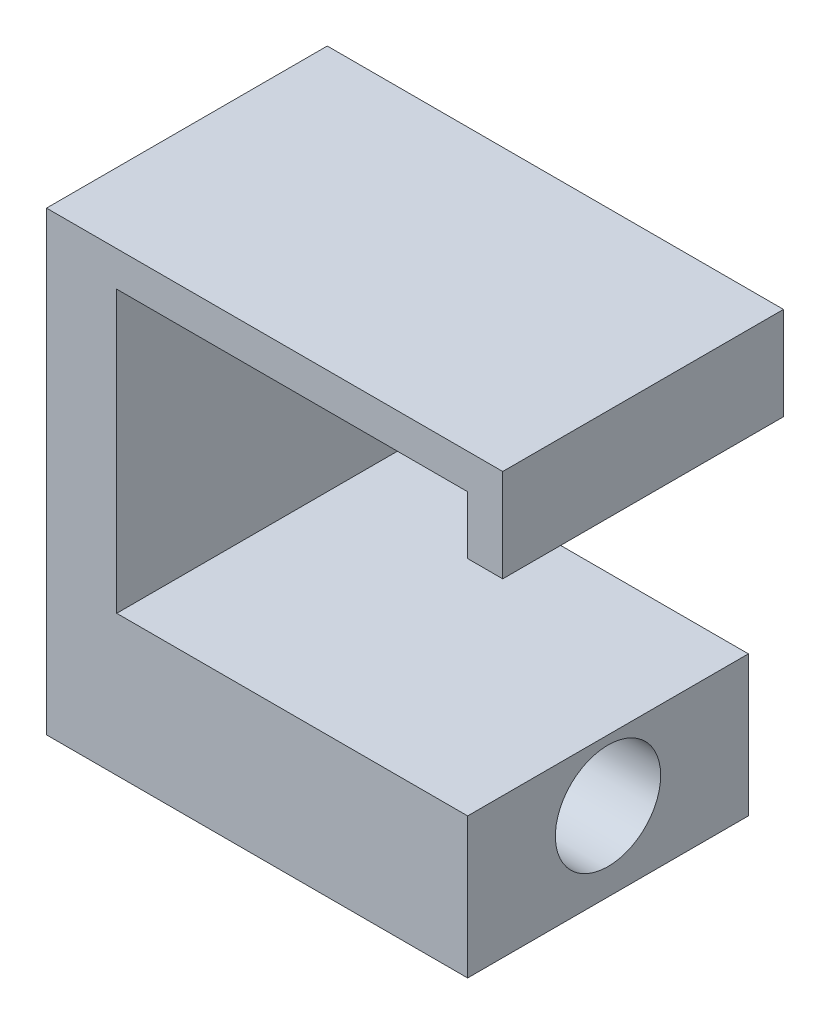
SolidWorks part; units mm, degrees
ref_plane "Front Plane" through (0, 0, 0) normal (0, 0, 1) x (1, 0, 0)
ref_plane "Top Plane" through (0, 0, 0) normal (0, 1, 0) x (1, 0, 0)
ref_plane "Right Plane" through (0, 0, 0) normal (1, 0, 0) x (0, 0, -1)
sketch "Sketch1" plane through (0, 0, 0) normal (0, 0, 1) x (1, 0, 0)
  line L0 (11.0331, 4.6037) -> (12.6206, 4.6037)
  line L1 (12.6206, 4.6037) -> (12.6206, 8.8106)
  line L2 (12.6206, 8.8106) -> (-8.0169, 8.8106)
  line L3 (-8.0169, 8.8106) -> (-8.0169, -11.8269)
  line L4 (-8.0169, -11.8269) -> (11.0331, -11.8269)
  line L5 (11.0331, -11.8269) -> (11.0331, -5.4769)
  line L6 (11.0331, -5.4769) -> (-4.8419, -5.4769)
  line L7 (-4.8419, -5.4769) -> (-4.8419, 7.2231)
  line L9 (-4.8419, 7.2231) -> (11.0331, 7.2231)
  line L10 (11.0331, 7.2231) -> (11.0331, 4.6037)
  line L11 (11.0331, 7.2231) -> (11.0331, 4.0481) construction
  line L12 (-4.8419, 7.2231) -> (-4.8419, 0.2381) construction
  line L13 (204.7081, 7.2231) -> (-4.8419, 7.2231) construction
  line L14 (-1.9209, -5.4769) -> (201.7871, -5.4769) construction
  point P11 (-4.6831, 6.8443)
  dimension "D1" = 1.5875
  dimension "D2" = 6.35
  dimension "D3" = 1.5875
  dimension "D4" = 3.175
extrude "Boss-Extrude1" add sketch "Sketch1" along normal blind 12.7
sketch "Sketch2" plane through (11.0331, 0, 0) normal (1, 0, 0) x (0, 0, -1)
  line L1 (-12.7, -11.8269) -> (0, -11.8269) construction
  line L2 (-6.35, -5.8738) -> (-6.35, -5.4769) construction
  line L3 (-12.7, -5.4769) -> (0, -5.4769) construction
  circle A0 centre (-6.35, -8.255) radius 2.3813
  point P6 (-6.35, -11.8269)
  dimension "D1" = 4.7625
  dimension "D2" = 0.3969
extrude "Cut-Extrude2" cut sketch "Sketch2" against normal through all
